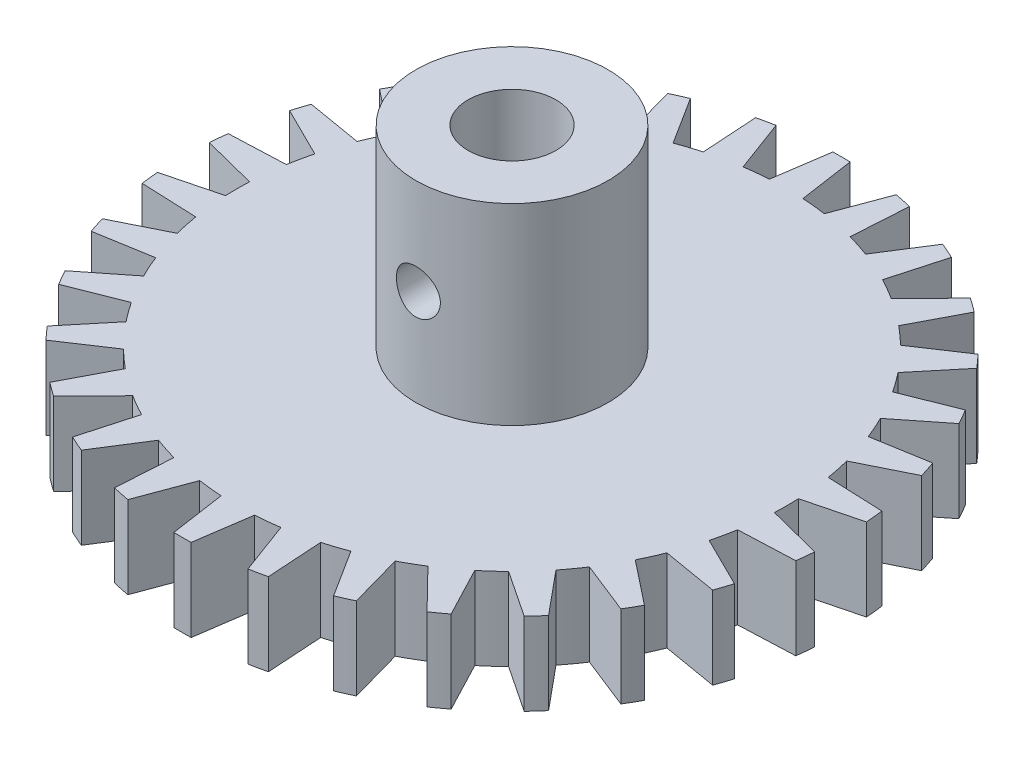
SolidWorks part; units mm, degrees
ref_plane "Front Plane" through (0, 0, 0) normal (0, 0, 1) x (1, 0, 0)
ref_plane "Top Plane" through (0, 0, 0) normal (0, 1, 0) x (1, 0, 0)
ref_plane "Right Plane" through (0, 0, 0) normal (1, 0, 0) x (0, 0, -1)
sketch "Sketch1" plane through (0, 0, 0) normal (0, 1, 0) x (1, 0, 0)
  line L0 (0, 0) -> (0, 12) construction
  line L1 (0, 0) -> (-0.3141, 11.9959) construction
  line L2 (0, 0) -> (-0.6105, 9.9813) construction
  line L3 (0, 0) -> (-1.0453, 9.9452) construction
  line L4 (-0.3141, 11.9959) -> (-0.6105, 9.9813)
  line L5 (0.3141, 11.9959) -> (0.6105, 9.9813)
  line L6 (2.1868, 11.7991) -> (1.4781, 9.8902)
  line L7 (2.8013, 11.6684) -> (2.6724, 9.6363)
  line L8 (4.5922, 11.0866) -> (3.5021, 9.3667)
  line L9 (5.1661, 10.831) -> (4.6175, 8.8701)
  line L10 (6.7969, 9.8895) -> (5.373, 8.4339)
  line L11 (7.3051, 9.5202) -> (6.3608, 7.7162)
  line L12 (8.7045, 8.2603) -> (7.0091, 7.1325)
  line L13 (9.1249, 7.7934) -> (7.8261, 6.2251)
  line L14 (10.2317, 6.27) -> (8.3389, 5.5194)
  line L15 (10.5458, 5.7259) -> (8.9493, 4.462)
  line L16 (11.3117, 4.0057) -> (9.3042, 3.665)
  line L17 (11.5058, 3.4082) -> (9.6815, 2.5038)
  line L18 (11.8973, 1.5663) -> (9.8629, 1.6505)
  line L19 (11.963, 0.9415) -> (9.9905, 0.4362)
  line L20 (11.963, -0.9415) -> (9.9905, -0.4362)
  line L21 (11.8973, -1.5663) -> (9.8629, -1.6505)
  line L22 (11.5058, -3.4082) -> (9.6815, -2.5038)
  line L23 (11.3117, -4.0057) -> (9.3042, -3.665)
  line L24 (10.5458, -5.7259) -> (8.9493, -4.462)
  line L25 (10.2317, -6.27) -> (8.3389, -5.5194)
  line L26 (9.1249, -7.7934) -> (7.8261, -6.2251)
  line L27 (8.7045, -8.2603) -> (7.0091, -7.1325)
  line L28 (7.3051, -9.5202) -> (6.3608, -7.7162)
  line L29 (6.7969, -9.8895) -> (5.373, -8.4339)
  line L30 (5.1661, -10.831) -> (4.6175, -8.8701)
  line L31 (4.5922, -11.0866) -> (3.5021, -9.3667)
  line L32 (2.8013, -11.6684) -> (2.6724, -9.6363)
  line L33 (2.1868, -11.7991) -> (1.4781, -9.8902)
  line L34 (0.3141, -11.9959) -> (0.6105, -9.9813)
  line L35 (-0.3141, -11.9959) -> (-0.6105, -9.9813)
  line L36 (-2.1868, -11.7991) -> (-1.4781, -9.8902)
  line L37 (-2.8013, -11.6684) -> (-2.6724, -9.6363)
  line L38 (-4.5922, -11.0866) -> (-3.5021, -9.3667)
  line L39 (-5.1661, -10.831) -> (-4.6175, -8.8701)
  line L40 (-6.7969, -9.8895) -> (-5.373, -8.4339)
  line L41 (-7.3051, -9.5202) -> (-6.3608, -7.7162)
  line L42 (-8.7045, -8.2603) -> (-7.0091, -7.1325)
  line L43 (-9.1249, -7.7934) -> (-7.8261, -6.2251)
  line L44 (-10.2317, -6.27) -> (-8.3389, -5.5194)
  line L45 (-10.5458, -5.7259) -> (-8.9493, -4.462)
  line L46 (-11.3117, -4.0057) -> (-9.3042, -3.665)
  line L47 (-11.5058, -3.4082) -> (-9.6815, -2.5038)
  line L48 (-11.8973, -1.5663) -> (-9.8629, -1.6505)
  line L49 (-11.963, -0.9415) -> (-9.9905, -0.4362)
  line L50 (-11.963, 0.9415) -> (-9.9905, 0.4362)
  line L51 (-11.8973, 1.5663) -> (-9.8629, 1.6505)
  line L52 (-11.5058, 3.4082) -> (-9.6815, 2.5038)
  line L53 (-11.3117, 4.0057) -> (-9.3042, 3.665)
  line L54 (-10.5458, 5.7259) -> (-8.9493, 4.462)
  line L55 (-10.2317, 6.27) -> (-8.3389, 5.5194)
  line L56 (-9.1249, 7.7934) -> (-7.8261, 6.2251)
  line L57 (-8.7045, 8.2603) -> (-7.0091, 7.1325)
  line L58 (-7.3051, 9.5202) -> (-6.3608, 7.7162)
  line L59 (-6.7969, 9.8895) -> (-5.373, 8.4339)
  line L60 (-5.1661, 10.831) -> (-4.6175, 8.8701)
  line L61 (-4.5922, 11.0866) -> (-3.5021, 9.3667)
  line L62 (-2.8013, 11.6684) -> (-2.6724, 9.6363)
  line L63 (-2.1868, 11.7991) -> (-1.4781, 9.8902)
  arc A0 (0.3141, 11.9959) -> (-0.3141, 11.9959) centre (0, 0) ccw
  arc A1 (-0.6105, 9.9813) -> (-1.0453, 9.9452) centre (0, 0) ccw
  arc A2 (0.6105, 9.9813) -> (1.0453, 9.9452) centre (0, 0) cw
  arc A4 (2.8013, 11.6684) -> (2.1868, 11.7991) centre (0, 0) ccw
  arc A5 (1.4781, 9.8902) -> (1.0453, 9.9452) centre (0, 0) ccw
  arc A6 (2.6724, 9.6363) -> (3.0902, 9.5106) centre (0, 0) cw
  arc A7 (5.1661, 10.831) -> (4.5922, 11.0866) centre (0, 0) ccw
  arc A8 (3.5021, 9.3667) -> (3.0902, 9.5106) centre (0, 0) ccw
  arc A9 (4.6175, 8.8701) -> (5, 8.6603) centre (0, 0) cw
  arc A10 (7.3051, 9.5202) -> (6.7969, 9.8895) centre (0, 0) ccw
  arc A11 (5.373, 8.4339) -> (5, 8.6603) centre (0, 0) ccw
  arc A12 (6.3608, 7.7162) -> (6.6913, 7.4314) centre (0, 0) cw
  arc A13 (9.1249, 7.7934) -> (8.7045, 8.2603) centre (0, 0) ccw
  arc A14 (7.0091, 7.1325) -> (6.6913, 7.4314) centre (0, 0) ccw
  arc A15 (7.8261, 6.2251) -> (8.0902, 5.8779) centre (0, 0) cw
  arc A16 (10.5458, 5.7259) -> (10.2317, 6.27) centre (0, 0) ccw
  arc A17 (8.3389, 5.5194) -> (8.0902, 5.8779) centre (0, 0) ccw
  arc A18 (8.9493, 4.462) -> (9.1355, 4.0674) centre (0, 0) cw
  arc A19 (11.5058, 3.4082) -> (11.3117, 4.0057) centre (0, 0) ccw
  arc A20 (9.3042, 3.665) -> (9.1355, 4.0674) centre (0, 0) ccw
  arc A21 (9.6815, 2.5038) -> (9.7815, 2.0791) centre (0, 0) cw
  arc A22 (11.963, 0.9415) -> (11.8973, 1.5663) centre (0, 0) ccw
  arc A23 (9.8629, 1.6505) -> (9.7815, 2.0791) centre (0, 0) ccw
  arc A24 (9.9905, 0.4362) -> (10, 0) centre (0, 0) cw
  arc A25 (11.8973, -1.5663) -> (11.963, -0.9415) centre (0, 0) ccw
  arc A26 (9.9905, -0.4362) -> (10, 0) centre (0, 0) ccw
  arc A27 (9.8629, -1.6505) -> (9.7815, -2.0791) centre (0, 0) cw
  arc A28 (11.3117, -4.0057) -> (11.5058, -3.4082) centre (0, 0) ccw
  arc A29 (9.6815, -2.5038) -> (9.7815, -2.0791) centre (0, 0) ccw
  arc A30 (9.3042, -3.665) -> (9.1355, -4.0674) centre (0, 0) cw
  arc A31 (10.2317, -6.27) -> (10.5458, -5.7259) centre (0, 0) ccw
  arc A32 (8.9493, -4.462) -> (9.1355, -4.0674) centre (0, 0) ccw
  arc A33 (8.3389, -5.5194) -> (8.0902, -5.8779) centre (0, 0) cw
  arc A34 (8.7045, -8.2603) -> (9.1249, -7.7934) centre (0, 0) ccw
  arc A35 (7.8261, -6.2251) -> (8.0902, -5.8779) centre (0, 0) ccw
  arc A36 (7.0091, -7.1325) -> (6.6913, -7.4314) centre (0, 0) cw
  arc A37 (6.7969, -9.8895) -> (7.3051, -9.5202) centre (0, 0) ccw
  arc A38 (6.3608, -7.7162) -> (6.6913, -7.4314) centre (0, 0) ccw
  arc A39 (5.373, -8.4339) -> (5, -8.6603) centre (0, 0) cw
  arc A40 (4.5922, -11.0866) -> (5.1661, -10.831) centre (0, 0) ccw
  arc A41 (4.6175, -8.8701) -> (5, -8.6603) centre (0, 0) ccw
  arc A42 (3.5021, -9.3667) -> (3.0902, -9.5106) centre (0, 0) cw
  arc A43 (2.1868, -11.7991) -> (2.8013, -11.6684) centre (0, 0) ccw
  arc A44 (2.6724, -9.6363) -> (3.0902, -9.5106) centre (0, 0) ccw
  arc A45 (1.4781, -9.8902) -> (1.0453, -9.9452) centre (0, 0) cw
  arc A46 (-0.3141, -11.9959) -> (0.3141, -11.9959) centre (0, 0) ccw
  arc A47 (0.6105, -9.9813) -> (1.0453, -9.9452) centre (0, 0) ccw
  arc A48 (-0.6105, -9.9813) -> (-1.0453, -9.9452) centre (0, 0) cw
  arc A49 (-2.8013, -11.6684) -> (-2.1868, -11.7991) centre (0, 0) ccw
  arc A50 (-1.4781, -9.8902) -> (-1.0453, -9.9452) centre (0, 0) ccw
  arc A51 (-2.6724, -9.6363) -> (-3.0902, -9.5106) centre (0, 0) cw
  arc A52 (-5.1661, -10.831) -> (-4.5922, -11.0866) centre (0, 0) ccw
  arc A53 (-3.5021, -9.3667) -> (-3.0902, -9.5106) centre (0, 0) ccw
  arc A54 (-4.6175, -8.8701) -> (-5, -8.6603) centre (0, 0) cw
  arc A55 (-7.3051, -9.5202) -> (-6.7969, -9.8895) centre (0, 0) ccw
  arc A56 (-5.373, -8.4339) -> (-5, -8.6603) centre (0, 0) ccw
  arc A57 (-6.3608, -7.7162) -> (-6.6913, -7.4314) centre (0, 0) cw
  arc A58 (-9.1249, -7.7934) -> (-8.7045, -8.2603) centre (0, 0) ccw
  arc A59 (-7.0091, -7.1325) -> (-6.6913, -7.4314) centre (0, 0) ccw
  arc A60 (-7.8261, -6.2251) -> (-8.0902, -5.8779) centre (0, 0) cw
  arc A61 (-10.5458, -5.7259) -> (-10.2317, -6.27) centre (0, 0) ccw
  arc A62 (-8.3389, -5.5194) -> (-8.0902, -5.8779) centre (0, 0) ccw
  arc A63 (-8.9493, -4.462) -> (-9.1355, -4.0674) centre (0, 0) cw
  arc A64 (-11.5058, -3.4082) -> (-11.3117, -4.0057) centre (0, 0) ccw
  arc A65 (-9.3042, -3.665) -> (-9.1355, -4.0674) centre (0, 0) ccw
  arc A66 (-9.6815, -2.5038) -> (-9.7815, -2.0791) centre (0, 0) cw
  arc A67 (-11.963, -0.9415) -> (-11.8973, -1.5663) centre (0, 0) ccw
  arc A68 (-9.8629, -1.6505) -> (-9.7815, -2.0791) centre (0, 0) ccw
  arc A69 (-9.9905, -0.4362) -> (-10, 0) centre (0, 0) cw
  arc A70 (-11.8973, 1.5663) -> (-11.963, 0.9415) centre (0, 0) ccw
  arc A71 (-9.9905, 0.4362) -> (-10, 0) centre (0, 0) ccw
  arc A72 (-9.8629, 1.6505) -> (-9.7815, 2.0791) centre (0, 0) cw
  arc A73 (-11.3117, 4.0057) -> (-11.5058, 3.4082) centre (0, 0) ccw
  arc A74 (-9.6815, 2.5038) -> (-9.7815, 2.0791) centre (0, 0) ccw
  arc A75 (-9.3042, 3.665) -> (-9.1355, 4.0674) centre (0, 0) cw
  arc A76 (-10.2317, 6.27) -> (-10.5458, 5.7259) centre (0, 0) ccw
  arc A77 (-8.9493, 4.462) -> (-9.1355, 4.0674) centre (0, 0) ccw
  arc A78 (-8.3389, 5.5194) -> (-8.0902, 5.8779) centre (0, 0) cw
  arc A79 (-8.7045, 8.2603) -> (-9.1249, 7.7934) centre (0, 0) ccw
  arc A80 (-7.8261, 6.2251) -> (-8.0902, 5.8779) centre (0, 0) ccw
  arc A81 (-7.0091, 7.1325) -> (-6.6913, 7.4314) centre (0, 0) cw
  arc A82 (-6.7969, 9.8895) -> (-7.3051, 9.5202) centre (0, 0) ccw
  arc A83 (-6.3608, 7.7162) -> (-6.6913, 7.4314) centre (0, 0) ccw
  arc A84 (-5.373, 8.4339) -> (-5, 8.6603) centre (0, 0) cw
  arc A85 (-4.5922, 11.0866) -> (-5.1661, 10.831) centre (0, 0) ccw
  arc A86 (-4.6175, 8.8701) -> (-5, 8.6603) centre (0, 0) ccw
  arc A87 (-3.5021, 9.3667) -> (-3.0902, 9.5106) centre (0, 0) cw
  arc A88 (-2.1868, 11.7991) -> (-2.8013, 11.6684) centre (0, 0) ccw
  arc A89 (-2.6724, 9.6363) -> (-3.0902, 9.5106) centre (0, 0) ccw
  arc A90 (-1.4781, 9.8902) -> (-1.0453, 9.9452) centre (0, 0) cw
  point P185 (0, 0)
  dimension "D1" = 1.5
  dimension "D2" = 2
  dimension "D3" = 2.5
  dimension "D4" = 30
  dimension "D5" = 10
extrude "Boss-Extrude1" add sketch "Sketch1" along normal blind 3
sketch "Sketch3" plane through (0, 3, 0) normal (0, 1, 0) x (1, 0, 0)
  circle A1 centre (0, 0) radius 3.5
  dimension "D2" = 7
extrude "Boss-Extrude2" add sketch "Sketch3" along normal blind 7
sketch "Sketch2" plane through (0, 3, 0) normal (0, 1, 0) x (1, 0, 0)
  circle A0 centre (0, 0) radius 1.6
  dimension "D1" = 3.2
extrude "Cut-Extrude1" cut sketch "Sketch2" against normal through all and the other way through all
sketch "Sketch4" plane through (0, 0, 0) normal (0, 0, 1) x (1, 0, 0)
  line L1 (3.5, 10) -> (-3.5, 10) construction
  circle A0 centre (0, 6.5) radius 0.8
  point P6 (-1.9738, 2.7481)
  dimension "D1" = 1.6
  dimension "D2" = 3.5
extrude "Cut-Extrude2" cut sketch "Sketch4" along normal through all
